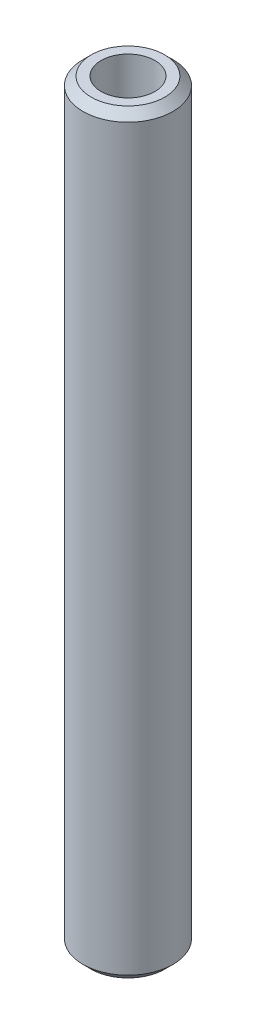
SolidWorks part; units mm, degrees
ref_plane "Front Plane" through (0, 0, 0) normal (0, 0, 1) x (1, 0, 0)
ref_plane "Top Plane" through (0, 0, 0) normal (0, 1, 0) x (1, 0, 0)
ref_plane "Right Plane" through (0, 0, 0) normal (1, 0, 0) x (0, 0, -1)
sketch "Sketch1" plane through (0, 0, 0) normal (0, 1, 0) x (1, 0, 0)
  circle A0 centre (0, 0) radius 30
  dimension "SHAFT_OD" = 60
extrude "Boss-Extrude1" add sketch "Sketch1" along normal blind 503.59
sketch "Sketch2" plane through (0, 0, 0) normal (0, 1, 0) x (1, 0, 0)
  circle A0 centre (0, 0) radius 17.9456
  dimension "BORE_D" = 35.8912
extrude "Cut-Extrude1" cut sketch "Sketch2" along normal through all
chamfer "Chamfer1" distance 5.4998 angle 45 2 edges at (0, 503.59, 30) (0, 0, 30)
